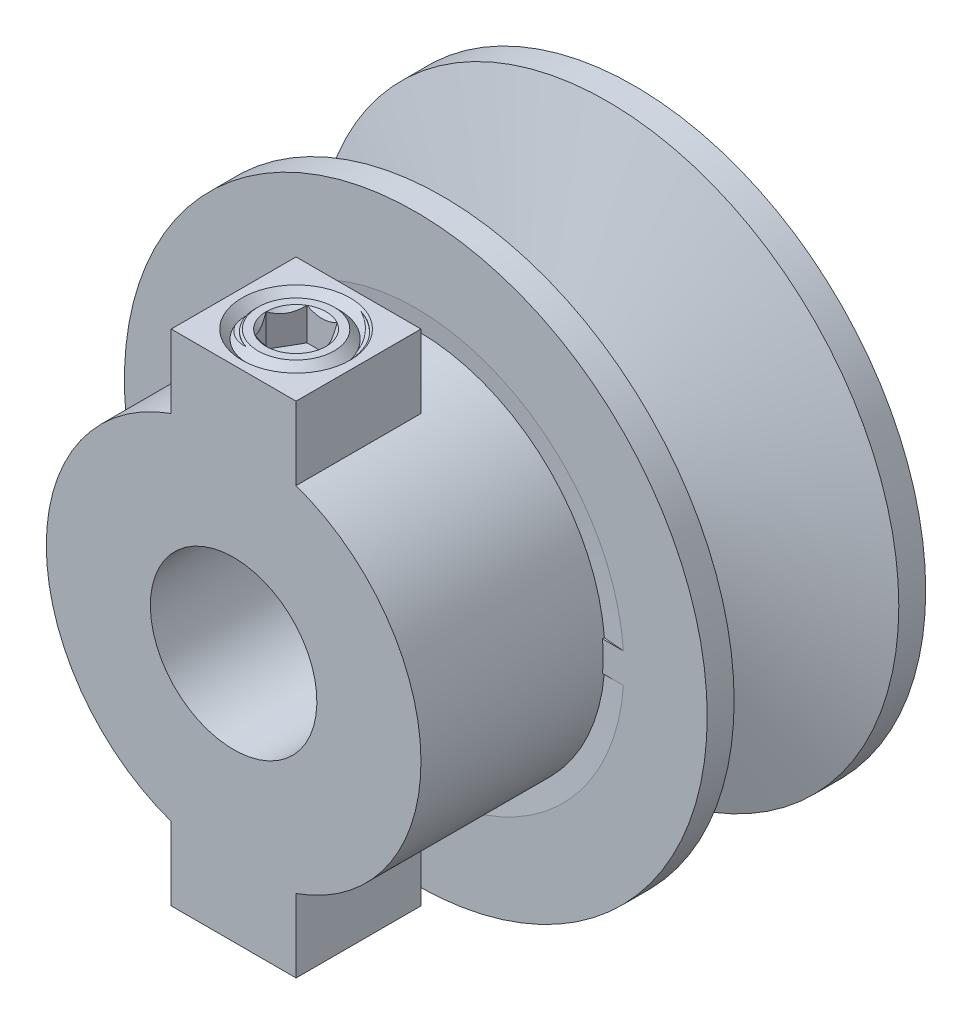
SolidWorks part; units mm, degrees
ref_plane "Front Plane" through (0, 0, 0) normal (0, 0, 1) x (1, 0, 0)
ref_plane "Top Plane" through (0, 0, 0) normal (0, 1, 0) x (1, 0, 0)
ref_plane "Right Plane" through (0, 0, 0) normal (1, 0, 0) x (0, 0, -1)
sketch "Sketch1" plane through (0, 0, 0) normal (1, 0, 0) x (0, 0, -1)
  line L0 (-22.225, 0) -> (8.3312, 0) construction
  line L1 (-6.2793, 22.225) -> (6.2793, 22.225) construction
  line L2 (6.2793, 22.225) -> (8.3312, 22.225)
  line L5 (-8.3312, 22.225) -> (6.2793, 22.225) construction
  line L7 (-22.225, 14.2875) -> (-22.225, -14.2875) construction
  line L10 (-8.3312, 15.875) -> (-8.1923, 14.2875)
  line L13 (-6.2793, 22.225) -> (-2.3965, 9.525)
  line L14 (-2.3965, 9.525) -> (2.3965, 9.525)
  line L15 (2.3965, 9.525) -> (6.2793, 22.225)
  line L16 (8.3312, 6.35) -> (-22.225, 6.35) construction
  line L17 (0, 22.225) -> (0, 0) construction
  line L18 (-6.2793, 22.225) -> (-8.3312, 22.225)
  line L20 (-22.225, 0) -> (-22.225, 6.35) construction
  line L22 (5.3086, 19.05) -> (-5.3086, 19.05) construction
  line L23 (8.3312, 22.225) -> (8.3312, 0) construction
  line L24 (8.3312, 15.875) -> (8.1923, 14.2875)
  line L26 (-22.225, 14.2875) -> (-8.7312, 14.2875)
  line L27 (-8.7312, 14.2875) -> (8.3312, 14.2875) construction
  line L28 (-8.3312, 19.05) -> (-5.3086, 19.05) construction
  line L31 (-22.225, 14.2875) -> (-22.225, 0)
  line L32 (-8.3312, 15.875) -> (-8.3312, 22.225)
  line L33 (8.3312, 22.225) -> (8.3312, 15.875)
  line L34 (-22.225, 0) -> (8.3312, 0)
  line L35 (8.3312, 0) -> (8.3312, 14.2875)
  line L37 (-8.1923, 14.2875) -> (8.1923, 14.2875) construction
  line L39 (-8.7312, 14.2875) -> (-8.1923, 14.2875)
  line L40 (8.3312, 14.2875) -> (8.1923, 14.2875)
  line L42 (-8.7312, 14.2875) -> (-8.7312, 0) construction
  point P6 (0, 14.2875)
  point P16 (0, 9.525)
  point P25 (-8.7312, 0)
  dimension "D1" = 5
revolve "Revolve1" add sketch "Sketch1" angle 360 about L0
sketch "Sketch2" plane through (0, 0, 0) normal (0, 1, 0) x (0, 0, -1)
  line L0 (-6.2793, 22.225) -> (-8.3312, 22.225) construction
  line L1 (-8.3312, 22.225) -> (-8.3312, -22.225) construction
  line L4 (-8.1701, 14.0335) -> (-8.3312, 15.875)
  line L5 (-8.1923, 14.2875) -> (-22.225, 14.2875) construction
  line L6 (-8.3312, 14.0335) -> (-8.1701, 14.0335)
  line L7 (-8.3312, 14.0335) -> (-8.3312, 15.875)
  line L8 (-8.1923, 14.2875) -> (-8.3312, 15.875) construction
  line L11 (8.3312, 14.0335) -> (8.1701, 14.0335)
  line L12 (8.1701, 14.0335) -> (8.3312, 15.875)
  line L13 (0, 0) -> (0, 22.225) construction
  line L14 (8.3312, 14.0335) -> (8.3312, 15.875)
  dimension "D1" = 0.254
extrude "Boss-Extrude1" add sketch "Sketch2" along normal mid plane 2.286
pattern_circular "CirPattern1" count 2 over 360 of "Boss-Extrude1"
sketch "Sketch3" plane through (0, 0, -8.3312) normal (0, 0, -1) x (-1, 0, 0)
  circle A0 centre (0, 0) radius 6.35
  circle A1 centre (0, 0) radius 19.05 construction
  point P4 (0, 6.35)
extrude "Cut-Extrude1" cut sketch "Sketch3" against normal up to vertex (30.5562 mm away) up to point (0, 0, 22.225)
sketch "Sketch4" [suppressed] plane through (0, 0, -8.1407) normal (0, 0, -1) x (-1, 0, 0)
  line L0 (2.3812, 7.9375) -> (-2.3812, 7.9375) construction
  line L1 (2.3813, 10.3187) -> (-2.3813, 10.3187)
  line L2 (2.3813, 10.3187) -> (2.3812, 5.5562)
  line L3 (2.3812, 5.5562) -> (-2.3812, 5.5562)
  line L4 (-2.3813, 10.3187) -> (-2.3812, 5.5562)
  dimension "Keyway Wd." = 3.175
  dimension "Keyway Dp." = 1.5875
extrude "Cut-Extrude2" [suppressed] cut sketch "Sketch4" against normal up to vertex
ref_plane "Plane1" through (0, 14.2875, 0) normal (0, 1, 0) x (-1, 0, 0)
sketch "Sketch5" plane through (0, 14.2875, 0) normal (0, 1, 0) x (-1, 0, 0)
  line L0 (0, 22.225) -> (0, 0) construction
  line L1 (4.7625, 12.7) -> (-4.7625, 12.7)
  line L2 (4.7625, 12.7) -> (4.7625, 22.225)
  line L3 (4.7625, 22.225) -> (-4.7625, 22.225)
  line L4 (-4.7625, 12.7) -> (-4.7625, 22.225)
  line L5 (14.2875, 22.225) -> (-14.2875, 22.225) construction
  dimension "D1" = 9.525
extrude "Boss-Extrude2" add sketch "Sketch5" against normal up to surface (5.5796 mm away) from offset 4.7625
mirror "Mirror1" about plane through (0, 0, 0) normal (0, 1, 0) of "Boss-Extrude2"
sketch "Sketch6" plane through (0, 19.05, 0) normal (0, 1, 0) x (-1, 0, 0)
  line L0 (0, 12.7) -> (0, 22.225) construction
  line L1 (4.7625, 22.225) -> (-4.7625, 22.225) construction
  line L2 (-4.7625, 12.7) -> (4.7625, 12.7) construction
  line L7 (0, 21.4312) -> (0, 20.0201) construction
  circle A0 centre (0, 17.4625) radius 3.9688 construction
  circle A1 centre (0, 17.4625) radius 3.0868
  dimension "D3" = 0.8819
extrude "Cut-Extrude3" cut sketch "Sketch6" against normal up to vertex up to point (0, 0, 22.225)
sketch "Sketch7" plane through (0, 19.05, 0) normal (0, 1, 0) x (-1, 0, 0)
  circle A0 centre (0, 17.4625) radius 3.9688 construction
  circle A1 centre (0, 17.4625) radius 3.9688
  point P3 (0, 21.4312)
curve "Helix/Spiral1" pitch 1.4111 height 15.6986 turns 11.125
sketch "Sketch8" plane through (0, 0, 0) normal (1, 0, 0) x (0, 0, -1)
  line L0 (-20.3619, 20.4611) -> (-20.3619, 19.05) construction
  line L1 (-20.3619, 19.05) -> (-21.584, 19.7556) construction
  line L2 (-21.584, 19.7556) -> (-20.3619, 20.4611) construction
  line L3 (-20.3619, 19.05) -> (-21.4312, 19.05) construction
  line L4 (-21.4312, 19.05) -> (-21.4312, 19.6674) construction
  line L5 (-21.4312, 19.6674) -> (-21.4312, 19.8438) construction
  line L6 (-20.5147, 19.1382) -> (-20.5147, 20.3729) construction
  line L7 (-21.584, 19.7556) -> (-21.4312, 19.7556) construction
  line L8 (-20.5147, 19.7556) -> (-20.3619, 19.7556) construction
  line L9 (-20.4383, 20.417) -> (-20.4383, 19.0941)
  line L10 (-20.4383, 19.0941) -> (-21.4312, 19.6674)
  line L11 (-21.4312, 19.6674) -> (-21.4312, 19.8438)
  line L12 (-21.4312, 19.8438) -> (-20.4383, 20.417)
  point P16 (-20.4383, 19.7556)
  dimension "D1" = 1.4111
  dimension "D2" = 0.1764
sweep "Cut-Sweep1" cut profiles "Sketch8" path "Helix/Spiral1"
sketch "Sketch9" plane through (0, 19.05, 0) normal (0, 1, 0) x (-1, 0, 0)
  circle A0 centre (0, 17.4625) radius 4.1215
extrude "Cut-Extrude4" cut sketch "Sketch9" against normal through all draft 45
sketch "Sketch10" plane through (0, 0, 0) normal (1, 0, 0) x (0, 0, -1)
  line L0 (-17.4625, 19.05) -> (-17.4625, 6.35) construction
  line L1 (-21.4313, 7.4193) -> (-21.4312, 17.9807)
  line L2 (-17.4625, 19.05) -> (-21.4312, 19.05) construction
  line L3 (-17.4625, 19.05) -> (-17.4625, 6.35)
  line L4 (-17.4625, 6.35) -> (-21.4312, 6.35) construction
  line L5 (-21.4312, 19.05) -> (-21.4312, 6.35) construction
  line L6 (-20.3619, 19.05) -> (-21.4312, 17.9807)
  line L7 (-21.4313, 7.4193) -> (-20.3619, 6.35)
  line L8 (-20.3619, 19.05) -> (-17.4625, 19.05)
  line L9 (-20.3619, 6.35) -> (-17.4625, 6.35)
  line L10 (-12.7, 19.05) -> (-22.225, 19.05) construction
  line L11 (-20.3619, 19.05) -> (-21.4312, 19.05) construction
  line L12 (-21.4312, 19.05) -> (-21.4312, 17.9807) construction
revolve "Revolve3" add sketch "Sketch10" angle 360 about L0
sketch "Sketch11" plane through (0, 19.05, 0) normal (0, 1, 0) x (-1, 0, 0)
  circle A1 centre (0, 17.4625) radius 3.9688
  circle A2 centre (0, 17.4625) radius 3.9688
  dimension "D1" = 0
curve "Helix/Spiral2" pitch 1.4111 height 14.1111 turns 10
sketch "Sketch12" plane through (0, 0, 0) normal (1, 0, 0) x (0, 0, -1)
  line L0 (-21.5076, 19.7115) -> (-21.5076, 18.3885)
  line L1 (-21.5076, 19.7556) -> (-21.5076, 19.7115) construction
  line L2 (-21.584, 19.7556) -> (-21.4312, 19.7556) construction
  line L3 (-20.3619, 19.05) -> (-21.584, 19.7556) construction
  line L4 (-21.5076, 19.7115) -> (-20.5147, 19.1382)
  line L5 (-20.5147, 19.1382) -> (-20.5147, 18.9618)
  line L6 (-20.5147, 18.9618) -> (-21.5076, 18.3885)
  line L7 (-21.584, 19.7556) -> (-20.3619, 19.05) construction
  line L8 (-20.3619, 19.05) -> (-21.584, 18.3444) construction
  line L9 (-21.584, 18.3444) -> (-21.584, 19.7556) construction
sweep "Cut-Sweep2" cut profiles "Sketch12" path "Helix/Spiral2"
sketch "Sketch13" plane through (0, 19.05, 0) normal (0, 1, 0) x (1, 0, 0)
  line L1 (2.2914, -17.4625) -> (1.1457, -15.4781)
  line L2 (1.1457, -15.4781) -> (-1.1457, -15.4781)
  line L3 (-1.1457, -15.4781) -> (-2.2914, -17.4625)
  line L4 (-2.2914, -17.4625) -> (-1.1457, -19.4469)
  line L5 (-1.1457, -19.4469) -> (1.1457, -19.4469)
  line L6 (1.1457, -19.4469) -> (2.2914, -17.4625)
  circle A0 centre (0, -17.4625) radius 1.9844 construction
  dimension "D1" = 3.9688
extrude "Cut-Extrude5" cut sketch "Sketch13" against normal blind 2.4805
sketch "Sketch14" plane through (0, 19.05, 0) normal (0, 1, 0) x (1, 0, 0)
  circle A0 centre (0, -17.4625) radius 2.2914
extrude "Cut-Extrude6" cut sketch "Sketch14" against normal through all draft 45
equation "\"D3@Sketch6\" = \"Screw Pitch@Sketch6\" * 5 / 8"
equation "\"D4@Helix/Spiral1\" = \"Screw Pitch@Sketch6\""
equation "\"D3@Helix/Spiral1\" = \"D4@Helix/Spiral1\" + ( \"Hub Dia.@Sketch1\" / 2 ) "
equation "\"D1@Sketch8\" = \"D4@Helix/Spiral1\""
equation "\"D2@Sketch8\" = \"D1@Sketch8\" / 8"
equation "\"D4@Helix/Spiral2\" = \"D4@Helix/Spiral1\""
equation "\"D3@Helix/Spiral2\" = \"D4@Helix/Spiral2\" + \"Screw Length@Sketch10\""
equation "\"D1@Sketch13\" = \"Screw OD@Sketch6\" / 2"
equation "\"D1@Cut-Extrude5\" = \"D1@Sketch13\" * 5 / 8"
